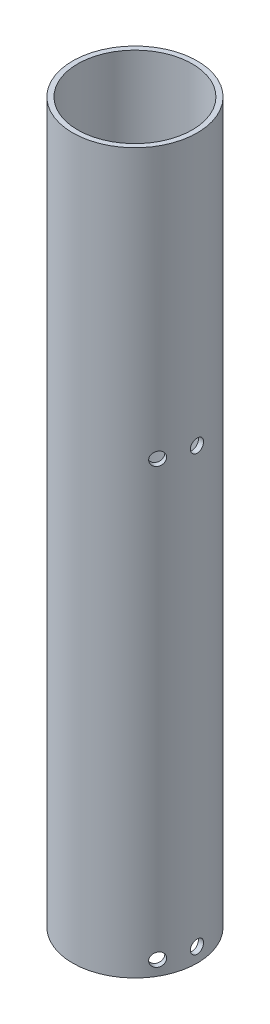
SolidWorks part; units mm, degrees
ref_plane "Front Plane" through (0, 0, 0) normal (0, 0, 1) x (1, 0, 0)
ref_plane "Top Plane" through (0, 0, 0) normal (0, 1, 0) x (1, 0, 0)
ref_plane "Right Plane" through (0, 0, 0) normal (1, 0, 0) x (0, 0, -1)
sketch "Sketch1" plane through (0, 0, 0) normal (0, 1, 0) x (1, 0, 0)
  circle A0 centre (0, 0) radius 26
  circle A1 centre (0, 0) radius 23.9
  dimension "D1" = 52
  dimension "D2" = 47.8
extrude "Boss-Extrude1" add sketch "Sketch1" along normal blind 300
sketch "Sketch3" plane through (0, 0, 0) normal (0, 0, 1) x (1, 0, 0)
  line L0 (0, 6) -> (0, 0)
  line L1 (0, 6) -> (0, 187)
  circle A0 centre (0, 6) radius 2.75
  circle A1 centre (0, 187) radius 2.75
  dimension "D2" = 5.5
  dimension "D3" = 5.5
  dimension "D1" = 6
  dimension "D4" = 181
extrude "Cut-Extrude2" cut sketch "Sketch3" against normal through all contours A1 | L1 A0 L0 | L0 A0 L1 region at (1.1671, 6, 0) region at (-1.1671, 6, 0) region at (-1.8895, 188.8895, 0)
pattern_circular "CirPattern1" count 3 over 360 about axis through (0, 300, 0) along (0, -1, 0) of "Cut-Extrude2"
sketch "Sketch5" plane through (0, 0, 0) normal (1, 0, 0) x (0, 0, -1)
  line L0 (0, 6) -> (0, 0)
  line L1 (0, 6) -> (0, 187)
  circle A0 centre (0, 187) radius 2.75
  circle A1 centre (0, 6) radius 2.75
  dimension "D2" = 5.5
  dimension "D1" = 6
  dimension "D4" = 5.5
  dimension "D3" = 181
extrude "Cut-Extrude3" cut sketch "Sketch5" against normal through all both and the other way through all contours A0 | L1 A1 L0 | L0 A1 L1 region at (0, 6, -1.1671) region at (0, 6, 1.1671) region at (0, 188.8895, 1.8895)
equation "\"TubeOutsideDiameter\"= 52"
equation "\"D1@Sketch1\"=\"TubeOutsideDiameter\""
equation "\"TubeInnerDiameter\"= 47.8"
equation "\"ReleaseMechanisumHeight\"=100"
equation "\"WireDiameter\"=3.38983"
equation "\"servoHoleDiameter\" = 2.8"
equation "\"CordDiameter\"= 5"
equation "\"MountingBoldDiameter\"=2.8"
equation "\"TubeMountingBoltDiameter\" = 5"
equation "\"D2@Sketch1\"=\"TubeInnerDiameter\""
equation "\"CardTubeOutsideDiameter\"= 54.2"
equation "\"CardTubeInsideDiameter\"= 50.4"
equation "\"D1@Sketch3\"=6"
equation "\"D2@Sketch3\"=\"TubeMountingBoltDiameter\"+0.5"
equation "\"D3@Sketch3\"=\"TubeMountingBoltDiameter\"+0.5"
equation "\"D2@Sketch5\"=\"TubeMountingBoltDiameter\"+0.5"
equation "\"D4@Sketch5\"=\"TubeMountingBoltDiameter\"+0.5"
